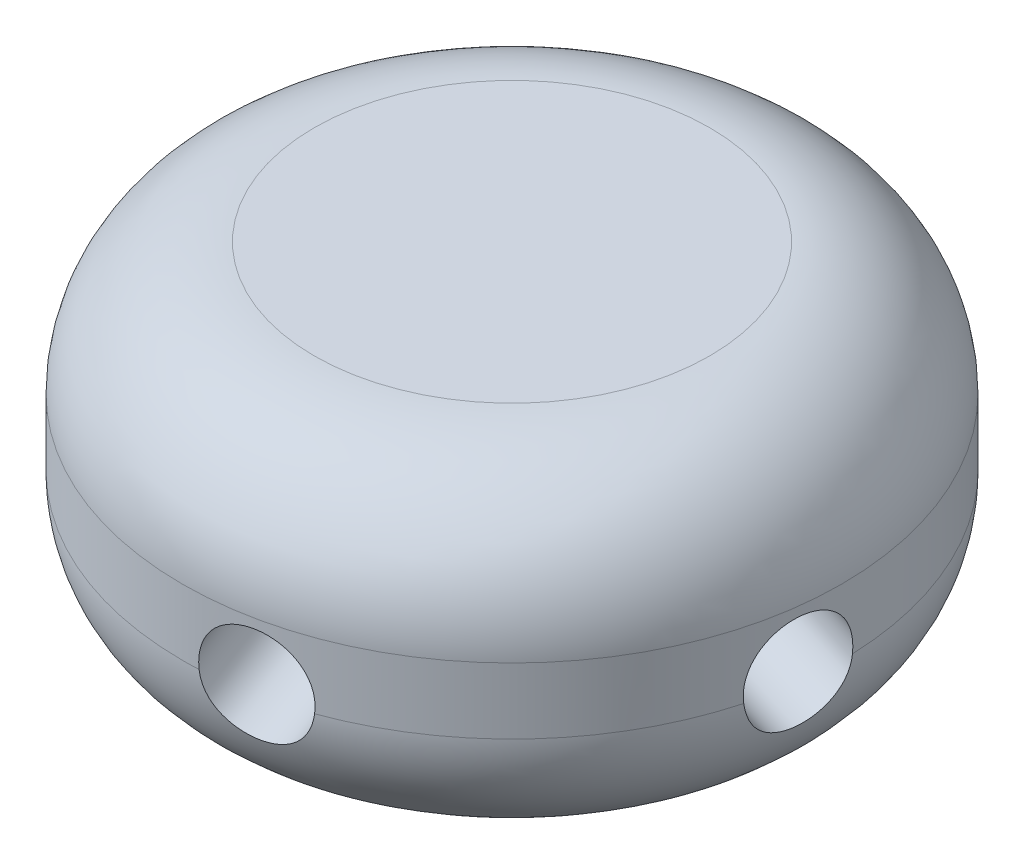
SolidWorks part; units mm, degrees
ref_plane "Front Plane" through (0, 0, 0) normal (0, 0, 1) x (1, 0, 0)
ref_plane "Top Plane" through (0, 0, 0) normal (0, 1, 0) x (1, 0, 0)
ref_plane "Right Plane" through (0, 0, 0) normal (1, 0, 0) x (0, 0, -1)
sketch "Sketch1" plane through (0, 0, 0) normal (0, 1, 0) x (1, 0, 0)
  circle A0 centre (0, 0) radius 10
  dimension "D1" = 20
extrude "Boss-Extrude1" add sketch "Sketch1" along normal blind 3 and the other way blind 7
ref_axis "5hubaxis" through (0, 5.5, 0) along (0, -1, 0)
ref_plane "holeplane" through (-3.3529, -1.0931, 1.8877) normal (0.8382, 0.2733, -0.4719) x (-0.4487, -0.1463, -0.8816)
sketch "Sketch4" plane through (-3.3529, -1.0931, 1.8877) normal (0.8382, 0.2733, -0.4719) x (-0.4487, -0.1463, -0.8816)
  circle A0 centre (0, 0) radius 1.5 construction
  circle A1 centre (0, 0) radius 1.5
extrude "hole" cut sketch "Sketch4" against normal through all
pattern_circular "holecir" count 5 over 360 about axis through (0, 5.5, 0) along (0, -1, 0) of "hole"
fillet "Fillet2" radius 4 2 edges at (0, -7, 10) (0, 3, 10)
